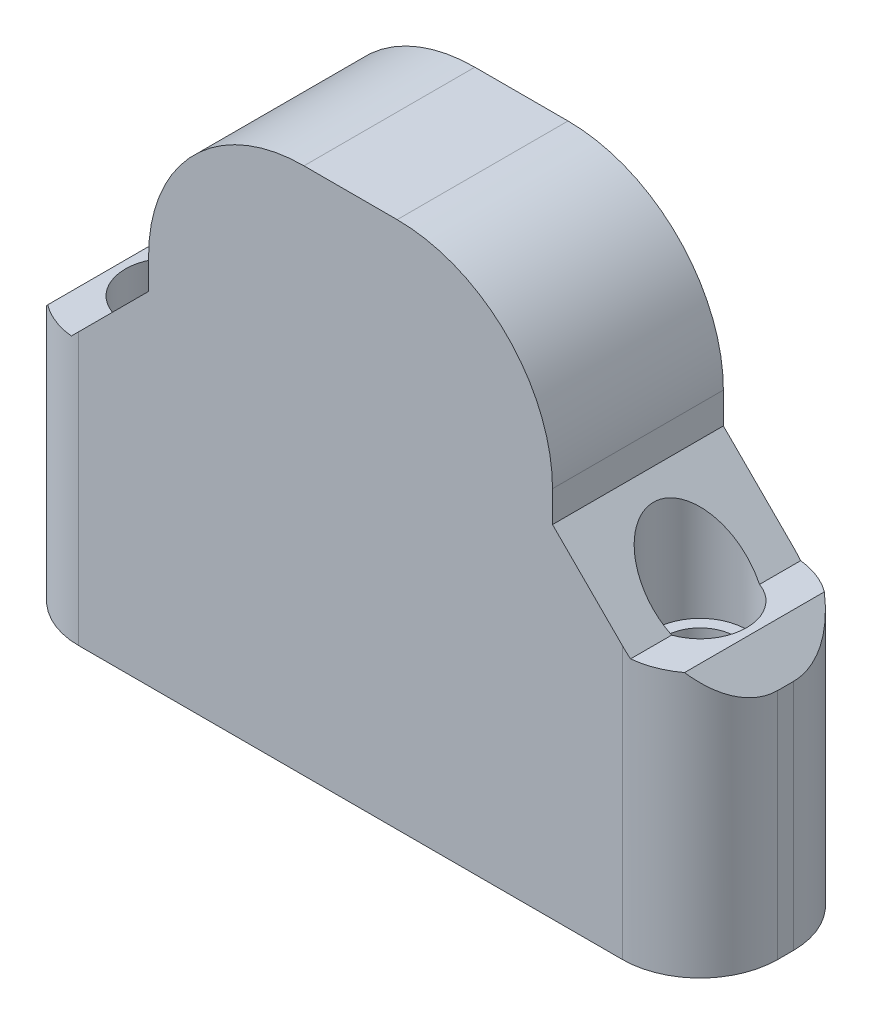
SolidWorks part; units mm, degrees
ref_plane "Alzado" through (0, 0, 0) normal (0, 0, 1) x (1, 0, 0)
ref_plane "Planta" through (0, 0, 0) normal (0, 1, 0) x (1, 0, 0)
ref_plane "Vista lateral" through (0, 0, 0) normal (1, 0, 0) x (0, 0, -1)
sketch "Croquis1" plane through (0, 0, 0) normal (0, 0, 1) x (1, 0, 0)
  line L0 (0, 0) -> (0, 22) construction
  line L1 (-22.5, 0) -> (22.5, 0)
  line L2 (-22.5, 0) -> (-22.5, 17)
  line L3 (-22.5, 17) -> (-13, 17)
  line L4 (22.5, 0) -> (22.5, 17)
  line L5 (22.5, 17) -> (13, 17)
  line L6 (-13, 17) -> (-13, 34)
  line L7 (-13, 34) -> (13, 34)
  line L8 (13, 34) -> (13, 17)
  circle A0 centre (0, 22) radius 8.5
  point P7 (0, 0)
  dimension "D2" = 17
  dimension "D1" = 22
  dimension "D3" = 45
  dimension "D4" = 26
  dimension "D5" = 17
  dimension "D6" = 17
extrude "Saliente-Extruir1" add sketch "Croquis1" along normal blind 6
sketch "Croquis2" plane through (0, 0, 6) normal (0, 0, 1) x (1, 0, 0)
  line L8 (22.5, 0) -> (22.5, 17)
  line L9 (22.5, 17) -> (13, 17)
  line L10 (13, 17) -> (13, 34)
  line L11 (13, 34) -> (-13, 34)
  line L12 (-13, 34) -> (-13, 17)
  line L13 (-13, 17) -> (-22.5, 17)
  line L14 (-22.5, 17) -> (-22.5, 0)
  line L15 (-22.5, 0) -> (22.5, 0)
  line L16 (22.5, 0) -> (22.5, 17)
  line L17 (22.5, 17) -> (13, 17)
  line L18 (13, 17) -> (13, 34)
  line L19 (13, 34) -> (-13, 34)
  line L20 (-13, 34) -> (-13, 17)
  line L21 (-13, 17) -> (-22.5, 17)
  line L22 (-22.5, 17) -> (-22.5, 0)
  line L23 (-22.5, 0) -> (22.5, 0)
  dimension "D1" = 0
extrude "Saliente-Extruir2" add sketch "Croquis2" along normal blind 5
sketch "Croquis3" plane through (0, 17, 0) normal (0, 1, 0) x (1, 0, 0)
  line L0 (17, -5.5) -> (-17, -5.5) construction
  line L1 (22.5, -11) -> (22.5, 0) construction
  line L2 (0, 0) -> (0, -5.5) construction
  point P3 (0, -5.5)
  point P6 (22.5, -5.5)
  dimension "D1" = 34
hole_wizard "Refrentado para tornillo con cabeza troncocónica de M41" positions "Croquis3D1" profile "Croquis4" counterbore size "M4" standard "Ansi Metric" end condition through all
sketch3d "Croquis3D1"
  point P0 (17, 17, 5.5)
  point P3 (-17, 17, 5.5)
sketch "Croquis4" plane through (17, 17, 5.5) normal (1, 0, 0) x (0, 0, 1)
  line L0 (0, 0) -> (0, 17)
  line L1 (0, 17) -> (2.25, 17)
  line L3 (2.25, 17) -> (2.25, 3.1)
  line L4 (2.25, 3.1) -> (3, 3.1)
  line L5 (3, 3.1) -> (3, 0)
  line L7 (3, 0) -> (0, 0)
  line L11 (0, -6.35) -> (0, 107.95) construction
  dimension "Diámetro de taladro hasta el siguiente" = 4.5
  dimension "Profundidad de taladro hasta el siguiente" = 17
  dimension "Diámetro de refrentado" = 6
  dimension "Profundidad de refrentado" = 3.1
chamfer "Chaflán1" distance 5 angle 45 2 edges at (13, 17, 5.5) (-13, 17, 5.5)
fillet "Redondeo1" radius 10 2 edges at (-13, 34, 5.5) (13, 34, 5.5)
chamfer "Chaflán2" distance 2 angle 45 2 edges at (-22.5, 17, 5.5) (22.5, 17, 5.5)
fillet "Redondeo2" radius 5 1 edges at (22.5, 7.5, 11)
fillet "Redondeo3" radius 5 1 edges at (-22.5, 7.5, 0)
fillet "Redondeo4" radius 5 1 edges at (22.5, 7.5, 0)
fillet "Redondeo5" radius 5 1 edges at (-22.5, 7.5, 11)
